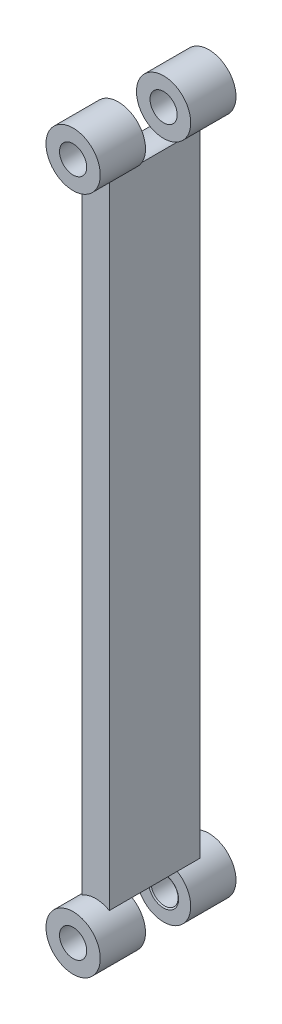
SolidWorks part; units mm, degrees
ref_plane "Alzado" through (0, 0, 0) normal (0, 0, 1) x (1, 0, 0)
ref_plane "Planta" through (0, 0, 0) normal (0, 1, 0) x (1, 0, 0)
ref_plane "Vista lateral" through (0, 0, 0) normal (1, 0, 0) x (0, 0, -1)
sketch "Croquis1" plane through (0, 0, 0) normal (0, 0, 1) x (1, 0, 0)
  line L0 (3, -37.5) -> (-3, -37.5)
  line L1 (1.5, -37.5) -> (-1.5, -37.5)
  line L2 (1.5, -37.5) -> (1.5, 37.5)
  line L3 (1.5, 37.5) -> (-1.5, 37.5)
  line L4 (-1.5, -37.5) -> (-1.5, 37.5)
  line L5 (1.5, -37.5) -> (-1.5, 37.5) construction
  line L6 (1.5, 37.5) -> (-1.5, -37.5) construction
  circle A0 centre (0, 37.5) radius 1.5
  circle A1 centre (0, -37.5) radius 1.5
  circle A2 centre (0, 37.5) radius 3
  circle A3 centre (0, -37.5) radius 3
  point P1 (0, 0)
  dimension "D3" = 6
  dimension "D4" = 6
  dimension "D5" = 3
  dimension "D1" = 3
  dimension "D2" = 75
extrude "Saliente-Extruir1" add sketch "Croquis1" along normal blind 5 and the other way blind 5 contours L3 L4 L1 L2
extrude "Saliente-Extruir3" add sketch "Croquis1<4>" along normal blind 7.5 and the other way blind 7.5 contours A1 | A3 | A0 | A2
sketch "Croquis1<4>" plane through (0, 0, 0) normal (0, 0, 1) x (1, 0, 0) same geometry as "Croquis1"
extrude "Cortar-Extruir1" cut sketch "Croquis1<5>" against normal blind 2.5 and the other way blind 2.5 contours A2 | A3
sketch "Croquis1<5>" plane through (0, 0, 0) normal (0, 0, 1) x (1, 0, 0) same geometry as "Croquis1"
extrude "Cortar-Extruir2" cut sketch "Croquis1<6>" against normal blind 10 and the other way blind 10 contours A1 | A0
sketch "Croquis1<6>" plane through (0, 0, 0) normal (0, 0, 1) x (1, 0, 0) same geometry as "Croquis1"
revolve "Cortar-Revolución2" cut sketch "Croquis1<11>" angle 360 about L0 region at (0, -40.4329, 0) region at (0, -38.1366, 0)
sketch "Croquis1<11>" plane through (0, 0, 0) normal (0, 0, 1) x (1, 0, 0) same geometry as "Croquis1"
